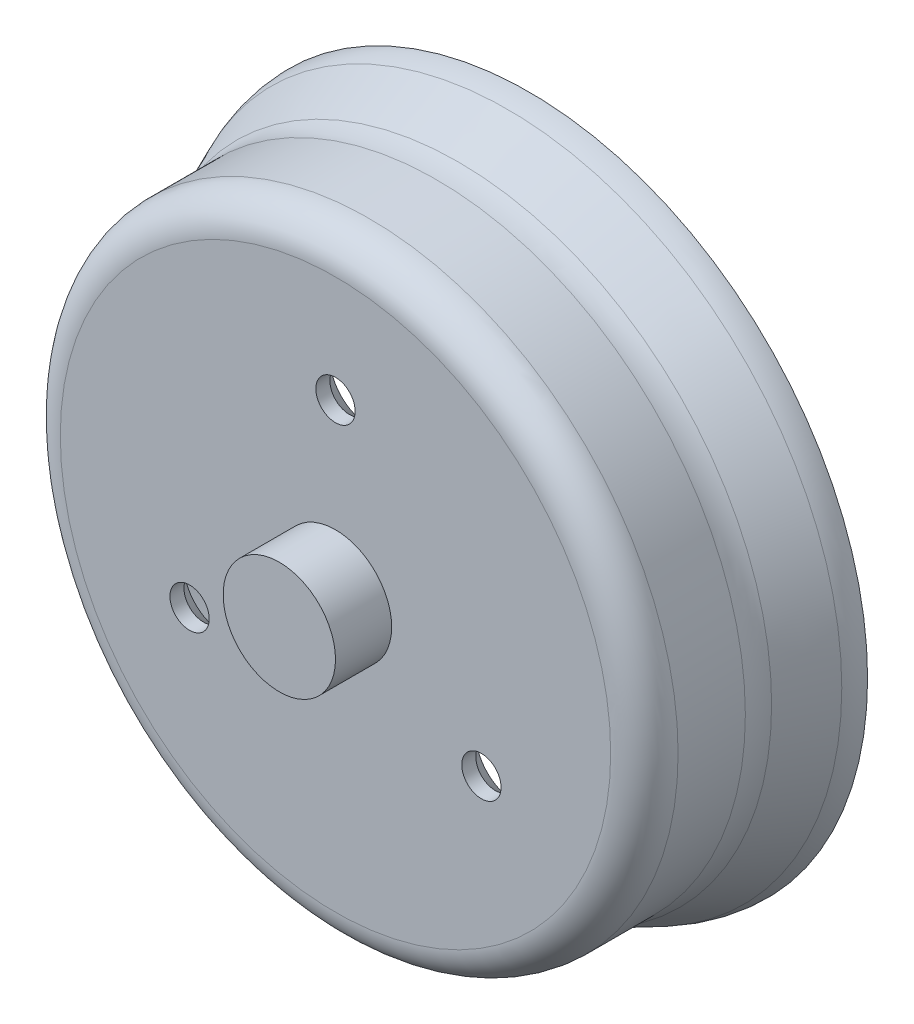
SolidWorks part; units mm, degrees
ref_plane "前视基准面" through (0, 0, 0) normal (0, 0, 1) x (1, 0, 0)
ref_plane "上视基准面" through (0, 0, 0) normal (0, 1, 0) x (1, 0, 0)
ref_plane "右视基准面" through (0, 0, 0) normal (1, 0, 0) x (0, 0, -1)
sketch "草图1" plane through (0, 0, 0) normal (0, 0, 1) x (1, 0, 0)
  circle A0 centre (0, 0) radius 27.5
  circle A1 centre (0, 0) radius 25.5
  dimension "D1" = 55
  dimension "D2" = 51
extrude "凸台-拉伸1" add sketch "草图1" along normal blind 10
sketch "草图2" plane through (0, 0, 10) normal (0, 0, 1) x (1, 0, 0)
  circle A0 centre (0, 0) radius 27.5
  circle A1 centre (0, 0) radius 27.5 construction
extrude "凸台-拉伸2" add sketch "草图2" against normal blind 3
fillet "圆角1" radius 3 1 edges at (27.5, 0, 10)
sketch "草图3" plane through (0, 0, 10) normal (0, 0, 1) x (1, 0, 0)
  circle A0 centre (0, 0) radius 5
  dimension "D1" = 10
extrude "凸台-拉伸3" add sketch "草图3" along normal blind 5
ref_plane "基准面1" through (0, 0, 10) normal (0, 0, 1) x (1, 0, 0)
sketch "草图4" plane through (0, 0, 10) normal (0, 0, 1) x (1, 0, 0)
  circle A0 centre (0, 0) radius 15 construction
  circle A1 centre (0, 15) radius 1.75
  circle A2 centre (12.9904, -7.5) radius 1.75
  circle A3 centre (-12.9904, -7.5) radius 1.75
  point P12 (0, 0)
  dimension "D1" = 30
  dimension "D2" = 3.5
  dimension "D3" = 3
extrude "切除-拉伸1" cut sketch "草图4" against normal blind 10
chamfer "倒角1" distance 1.75 angle 45 3 edges at (14.7404, -7.5, 7) (-11.2404, -7.5, 7) (1.75, 15, 7)
sketch "草图5" plane through (0, 0, 0) normal (0, 1, 0) x (1, 0, 0)
  line L0 (27.5, 0) -> (31, 8.2916)
  line L1 (27.5, 0) -> (-27.5, 0) construction
  line L2 (27.5, -7) -> (27.5, 0) construction
  line L3 (31, 8.2916) -> (29, 8.2916)
  line L4 (29, 8.2916) -> (25.5, 0)
  line L5 (25.5, 0) -> (-25.5, 0) construction
  line L6 (25.5, 0) -> (27.5, 0)
  line L7 (0, -15) -> (0, 0) construction
  line L8 (-5, -15) -> (5, -15) construction
  dimension "D1" = 2
  dimension "D2" = 2
  dimension "D3" = 9
  dimension "D4" = 3.5
revolve "旋转1" add sketch "草图5" angle 360 about L7
fillet "圆角2" radius 5 1 edges at (25.5, 0, 0)
chamfer "倒角2" distance 2 angle 45 1 edges at (29, 0, -8.2916) first distance on face at (25.8936, 0, -0.9324)
fillet "圆角3" radius 5 1 edges at (28.2222, 0, -6.449)
fillet "圆角4" radius 5 2 edges at (-30.6363, 0, -7.43) (27.5, 0, 0)
